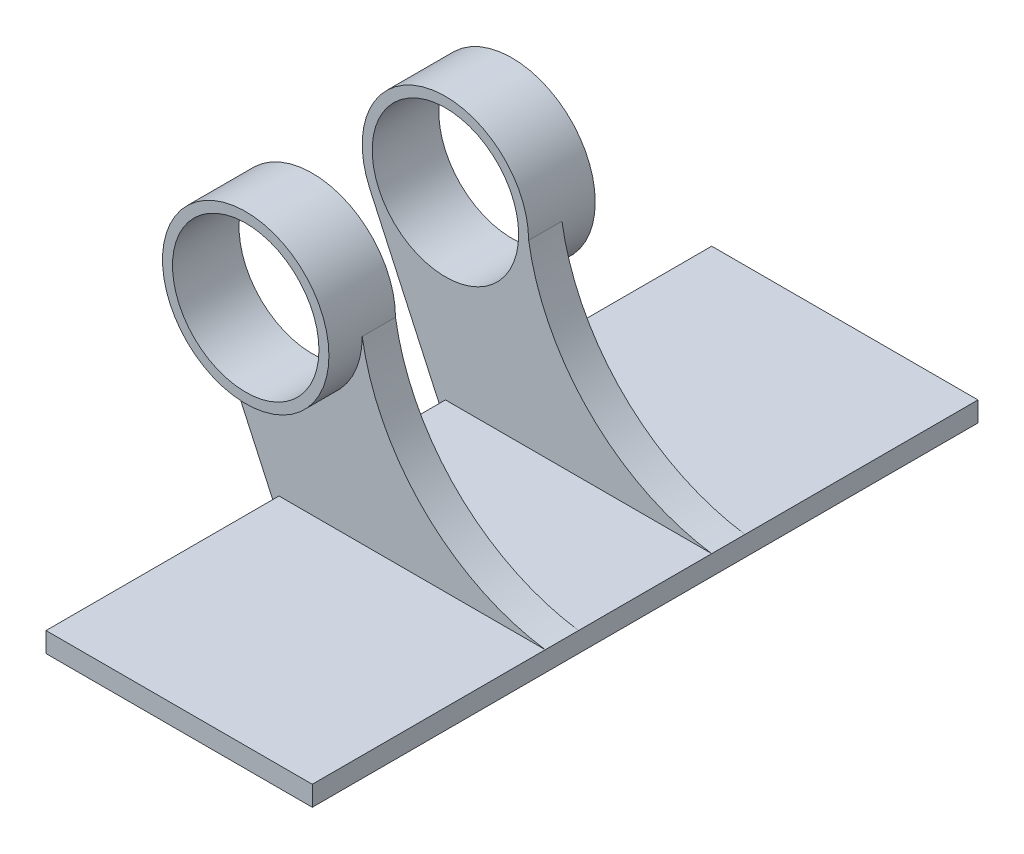
SolidWorks part; units mm, degrees
note: The reader was unsure of these and kept them because the rebuilt part matched: shared geometry of "Croquis2<4>", "Croquis2<6>", "Croquis2<7>".
ref_plane "Alzado" through (0, 0, 0) normal (0, 0, 1) x (1, 0, 0)
ref_plane "Planta" through (0, 0, 0) normal (0, 1, 0) x (1, 0, 0)
ref_plane "Vista lateral" through (0, 0, 0) normal (1, 0, 0) x (0, 0, -1)
sketch "Croquis2" plane through (0, 0, 0) normal (0, 0, 1) x (1, 0, 0)
  line L0 (0, 0) -> (0, -30) construction
  line L1 (40, -30) -> (0, -30)
  line L2 (40, -30) -> (40, -27)
  line L3 (40, -27) -> (0, -27)
  line L4 (0, -30) -> (0, -27)
  line L5 (40, -30) -> (0, -27) construction
  line L6 (40, -27) -> (0, -30) construction
  line L7 (0, -30) -> (-11.3632, -5.2083)
  circle A0 centre (0, 0) radius 12.5
  circle A2 centre (0, 0) radius 11
  arc A3 (12.5, 0) -> (40, -27) centre (44.638, 5.2285) ccw
  point P3 (20, -28.5)
  dimension "D1" = 25
  dimension "D7" = 22
  dimension "D2" = 3
  dimension "D3" = 30
  dimension "D4" = 40
extrude "Saliente-Extruir1" add sketch "Croquis2" along normal blind 10
extrude "Saliente-Extruir2" add sketch "Croquis2<4>" along normal blind 5
sketch "Croquis2<4>" plane through (0, 0, 0) normal (0, 0, 1) x (1, 0, 0) same geometry as "Croquis2"
ref_plane "Plano1" through (0, 0, -10) normal (0, 0, -1) x (-1, 0, 0)
extrude "Saliente-Extruir3" add sketch "Croquis2<6>" along normal blind 40
sketch "Croquis2<6>" plane through (0, 0, 0) normal (0, 0, 1) x (1, 0, 0) same geometry as "Croquis2"
mirror "Simetría2" about plane through (0, 0, -10) normal (0, 0, -1) of bodies 104 102
extrude "Saliente-Extruir4" add sketch "Croquis2<7>" along a picked direction on the side against the normal up to surface (20 mm away)
sketch "Croquis2<7>" plane through (0, 0, 0) normal (0, 0, 1) x (1, 0, 0) same geometry as "Croquis2"
